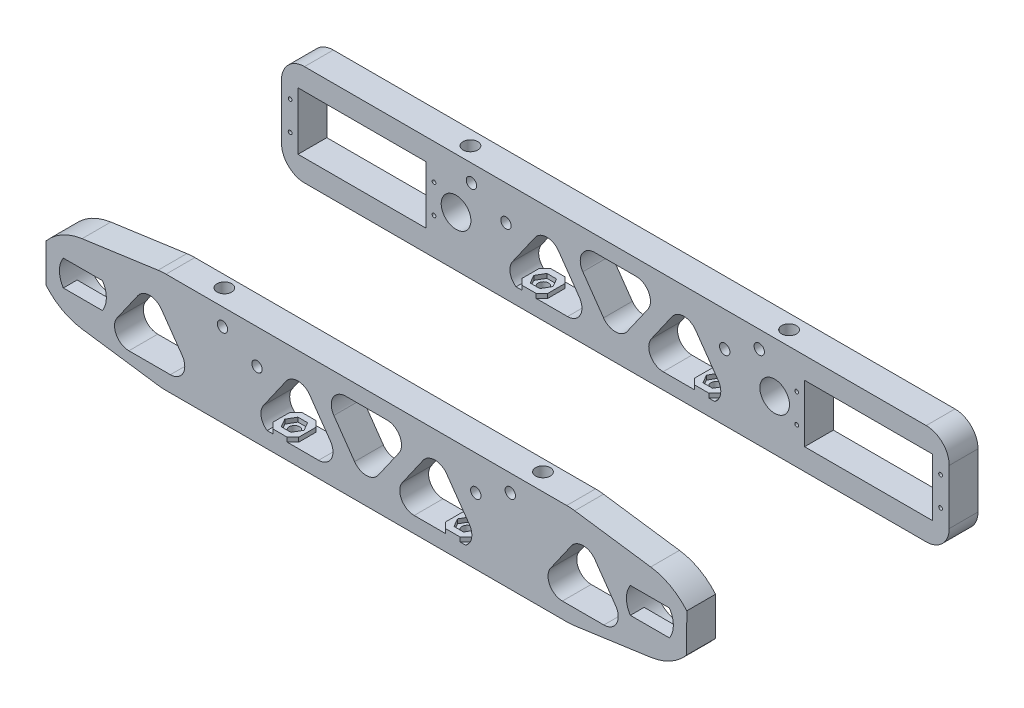
SolidWorks part; units mm, degrees
material "PLA 100% Infill"
ref_plane "Front Plane" through (0, 0, 0) normal (0, 0, 1) x (1, 0, 0)
ref_plane "Top Plane" through (0, 0, 0) normal (0, 1, 0) x (1, 0, 0)
ref_plane "Right Plane" through (0, 0, 0) normal (1, 0, 0) x (0, 0, -1)
sketch "Sketch1" plane through (0, 0, 0) normal (0, 0, 1) x (1, 0, 0)
  line L0 (-232, 17.5) -> (-148.2075, 17.5) construction
  line L1 (-232, 35) -> (0, 35)
  line L2 (-232, 35) -> (-232, 0)
  line L3 (-232, 0) -> (0, 0)
  line L4 (0, 35) -> (0, 0)
  line L5 (-116, 35) -> (-116, 17.5) construction
  line L6 (-156.61, 5.5) -> (-139.805, 29.5)
  line L7 (-139.805, 29.5) -> (-123, 5.5)
  line L8 (-123, 5.5) -> (-156.61, 5.5)
  line L9 (-132.805, 29.5) -> (-116, 5.5)
  line L10 (-116, 5.5) -> (-99.195, 29.5)
  line L11 (-99.195, 29.5) -> (-132.805, 29.5)
  line L12 (-139.805, 29.5) -> (-93.3936, 29.5) construction
  line L13 (-123, 5.5) -> (-123.2541, 5.5) construction
  line L14 (-74.6848, 5.5) -> (-74.6848, 29.5) construction
  line L21 (-116, 17.5) -> (-148.2075, 17.5) construction
  line L22 (-116, 17.5) -> (-83.7925, 17.5) construction
  line L23 (-92.195, 29.5) -> (-109, 5.5)
  line L24 (-75.39, 5.5) -> (-92.195, 29.5)
  line L25 (-109, 5.5) -> (-75.39, 5.5)
  line L27 (-116, 5.5) -> (-116, 0) construction
  circle A2 centre (-171.35, 17.5) radius 5.15
  circle A4 centre (-214.5, 17.5) radius 8.15
  circle A5 centre (-17.5, 17.5) radius 8.15
  circle A6 centre (-60.65, 17.5) radius 5.15
  point P12 (-176.5, 17.5)
  dimension "D2" = 35
  dimension "D3" = 16.3
  dimension "D4" = 10.3
  dimension "D5" = 232
  dimension "D6" = 43.15
  dimension "D7" = 24
  dimension "D9" = 7
  dimension "D10" = 110.7
  dimension "D8" = 70
extrude "Boss-Extrude1" add sketch "Sketch1" along normal blind 10 contours L4 A5 L1 L2 A4 L3 A2 A6 | A4 L2 | L4 A5 | A5 | A4 region at (-116, 32.6537, 0) region at (-214.5, 17.5, 0) region at (-17.5, 17.5, 0)
sketch "Sketch2" plane through (0, 0, 10) normal (0, 0, 1) x (1, 0, 0)
  circle A0 centre (-60.65, 17.5) radius 5.15 construction
  circle A1 centre (-60.65, 17.5) radius 5.15
  circle A2 centre (-171.35, 17.5) radius 5.15 construction
  circle A3 centre (-171.35, 17.5) radius 5.15
extrude "Boss-Extrude2" add sketch "Sketch2" against normal blind 2
ref_plane "Plane1" through (0, 0, -76.5) normal (0, 0, 1) x (1, 0, 0)
sketch "Sketch3" plane through (0, 0, -76.5) normal (0, 0, 1) x (1, 0, 0)
  line L0 (-232, 0) -> (0, 0) construction
  line L1 (-232, 35) -> (0, 35) construction
  line L2 (-232, 0) -> (0, 0)
  line L3 (-232, 35) -> (0, 35)
  line L4 (-181.75, 27.5) -> (-226.25, 27.5)
  line L5 (-181.75, 7.5) -> (-181.75, 27.5)
  line L6 (-226.25, 7.5) -> (-181.75, 7.5)
  line L7 (-226.25, 7.5) -> (-226.25, 27.5)
  line L8 (24, 17.5) -> (-237, 17.5) construction
  line L9 (-229, 22.7282) -> (-229, 12.7282) construction
  line L10 (-179, 22.7282) -> (-179, 12.7282) construction
  line L11 (-179, 12.7282) -> (-184.9311, 12.7282) construction
  line L12 (-116, 35) -> (-116, 0) construction
  line L13 (-50.25, 7.5) -> (-50.25, 27.5)
  line L14 (-5.75, 7.5) -> (-50.25, 7.5)
  line L15 (-5.75, 7.5) -> (-5.75, 27.5)
  line L16 (-50.25, 27.5) -> (-5.75, 27.5)
  line L18 (-92.195, 29.5) -> (-109, 5.5)
  line L21 (0, 35) -> (0, 0) construction
  line L22 (-232, 35) -> (-232, 0) construction
  line L23 (0, 35) -> (0, 0)
  line L24 (-232, 35) -> (-232, 0)
  line L31 (-116, 5.5) -> (-99.195, 29.5) construction
  line L32 (-99.195, 29.5) -> (-132.805, 29.5) construction
  line L33 (-132.805, 29.5) -> (-116, 5.5) construction
  line L34 (-123, 5.5) -> (-156.61, 5.5) construction
  line L35 (-139.805, 29.5) -> (-123, 5.5) construction
  line L36 (-156.61, 5.5) -> (-139.805, 29.5) construction
  line L43 (-116, 5.5) -> (-99.195, 29.5)
  line L44 (-99.195, 29.5) -> (-132.805, 29.5)
  line L45 (-132.805, 29.5) -> (-116, 5.5)
  line L46 (-123, 5.5) -> (-156.61, 5.5)
  line L47 (-139.805, 29.5) -> (-123, 5.5)
  line L48 (-156.61, 5.5) -> (-139.805, 29.5)
  line L49 (-75.39, 5.5) -> (-92.195, 29.5)
  line L50 (-109, 5.5) -> (-75.39, 5.5)
  circle A4 centre (-179, 12.7282) radius 0.65
  circle A5 centre (-179, 22.7282) radius 0.65
  circle A6 centre (-229, 12.7282) radius 0.65
  circle A7 centre (-229, 22.7282) radius 0.65
  circle A8 centre (-171.35, 17.5) radius 5.15 construction
  circle A9 centre (-171.35, 17.5) radius 5.15
  circle A10 centre (-3, 22.7282) radius 0.65
  circle A11 centre (-3, 12.7282) radius 0.65
  circle A12 centre (-53, 12.7282) radius 0.65
  circle A13 centre (-53, 22.7282) radius 0.65
  circle A14 centre (-60.65, 17.5) radius 5.15
  point P5 (-191.5, 17.5)
  point P21 (-181.75, 17.5)
  dimension "D10" = 1.3
  dimension "D1" = 2.75
  dimension "D2" = 20
  dimension "D3" = 44.5
  dimension "D4" = 2.75
  dimension "D5" = 10
  dimension "D6" = 5.2282
  dimension "D7" = 9.75
  dimension "D8" = 10
  dimension "D9" = 131.5
extrude "Boss-Extrude3" add sketch "Sketch3" against normal blind 10 separate body
sketch "Sketch4" plane through (0, 35, 0) normal (0, 1, 0) x (1, 0, 0)
  line L0 (-116, 86.5) -> (-116, -10) construction
  line L1 (0, 86.5) -> (-232, 86.5) construction
  line L2 (-232, -10) -> (0, -10) construction
  line L3 (-171.35, 86.5) -> (-171.35, -10) construction
  line L4 (-243.5, -4) -> (17.5, -4) construction
  line L5 (0, 86.5) -> (0, 76.5) construction
  line L6 (-232, 86.5) -> (-232, 76.5) construction
  line L7 (0, 81.5) -> (-232, 81.5) construction
  line L10 (-177.85, 39) -> (-122.5, 39) construction
  line L11 (-232, -10) -> (0, -10) construction
  circle A4 centre (-171.35, -4) radius 2.55
  circle A11 centre (-60.65, -4) radius 2.55
  circle A12 centre (-171.35, 81.5) radius 2.55
  circle A13 centre (-60.65, 81.5) radius 2.55
  dimension "D1" = 0
  dimension "D4" = 5.1
  dimension "D2" = 55.35
  dimension "D5" = 6
  dimension "D6" = 43
extrude "Cut-Extrude1" cut sketch "Sketch4" against normal blind 10
chamfer "Chamfer1" distance 45 angle 8 4 edges at (0, 35, 5) (0, 0, 5) (-232, 0, 5) (-232, 35, 5) first distance on face at (-171.35, 35, 6.55) first distance on face at (-116, 0, 5)
fillet "Fillet1" radius 8 4 edges at (0, 0, -81.5) (0, 35, -81.5) (-232, 0, -81.5) (-232, 35, -81.5)
sketch "Sketch6" plane through (0, 0, 10) normal (0, 0, 1) x (1, 0, 0)
  line L0 (-116, 5.5) -> (-99.195, 29.5) construction
  line L1 (-174.5, 5.5) -> (-208.11, 5.5)
  line L2 (-132.805, 29.5) -> (-116, 5.5) construction
  line L3 (-208.11, 5.5) -> (-191.305, 29.5)
  line L4 (-139.805, 29.5) -> (-123, 5.5) construction
  line L5 (-156.61, 5.5) -> (-139.805, 29.5) construction
  line L6 (-116, 5.5) -> (-99.195, 29.5)
  line L7 (-99.195, 29.5) -> (-132.805, 29.5)
  line L8 (-132.805, 29.5) -> (-116, 5.5)
  line L9 (-123, 5.5) -> (-156.61, 5.5)
  line L10 (-139.805, 29.5) -> (-123, 5.5)
  line L11 (-156.61, 5.5) -> (-139.805, 29.5)
  line L12 (-191.305, 29.5) -> (-174.5, 5.5)
  line L13 (-109, 5.5) -> (-75.39, 5.5) construction
  line L14 (-75.39, 5.5) -> (-92.195, 29.5) construction
  line L15 (-92.195, 29.5) -> (-109, 5.5) construction
  line L16 (-109, 5.5) -> (-75.39, 5.5)
  line L17 (-75.39, 5.5) -> (-92.195, 29.5)
  line L18 (-92.195, 29.5) -> (-109, 5.5)
  line L19 (-57.5, 5.5) -> (-23.89, 5.5)
  line L20 (-23.89, 5.5) -> (-40.695, 29.5)
  line L21 (-40.695, 29.5) -> (-57.5, 5.5)
  dimension "D3" = 51.5
  dimension "D4" = 51.5
  dimension "D1" = 2
  dimension "D2" = 2
extrude "Cut-Extrude3" cut sketch "Sketch6" against normal blind 10 contours L20 L21 L19 | L1 L3 L12 region at (-40.695, 13.5, 10)
sketch "Sketch7" plane through (0, 5.5, 0) normal (0, 1, 0) x (1, 0, 0)
  line L0 (-156.61, 81.5) -> (-75.39, 81.5) construction
  line L1 (-156.61, 86.5) -> (-156.61, 76.5) construction
  line L2 (-75.39, 86.5) -> (-75.39, 76.5) construction
  line L3 (-227.4452, 0) -> (-227.4452, 76.5) construction
  line L4 (-187, 0) -> (-45, 0) construction
  line L5 (-226.25, 76.5) -> (-181.75, 76.5) construction
  line L6 (-227.4452, 38.25) -> (0, 38.25) construction
  line L7 (0, 38.25) -> (0, 0) construction
  line L8 (-116, 81.5) -> (-116, -5) construction
  line L9 (-116, -10) -> (-116, 0) construction
  line L10 (-149.3486, 81.5) -> (-147.6743, 84.4)
  line L11 (-147.6743, 84.4) -> (-144.3257, 84.4)
  line L12 (-144.3257, 84.4) -> (-142.6514, 81.5)
  line L13 (-142.6514, 81.5) -> (-144.3257, 78.6)
  line L14 (-144.3257, 78.6) -> (-147.6743, 78.6)
  line L15 (-147.6743, 78.6) -> (-149.3486, 81.5)
  line L16 (-144.3257, 84.4) -> (-147.6743, 78.6) construction
  line L17 (-84.3257, 78.6) -> (-82.6514, 81.5)
  line L18 (-87.6743, 78.6) -> (-84.3257, 78.6)
  line L19 (-89.3486, 81.5) -> (-87.6743, 78.6)
  line L20 (-87.6743, 84.4) -> (-89.3486, 81.5)
  line L21 (-84.3257, 84.4) -> (-87.6743, 84.4)
  line L22 (-82.6514, 81.5) -> (-84.3257, 84.4)
  line L23 (-87.6743, -2.1) -> (-84.3257, -2.1)
  line L24 (-89.3486, -5) -> (-87.6743, -2.1)
  line L25 (-87.6743, -7.9) -> (-89.3486, -5)
  line L26 (-84.3257, -7.9) -> (-87.6743, -7.9)
  line L27 (-82.6514, -5) -> (-84.3257, -7.9)
  line L28 (-84.3257, -2.1) -> (-82.6514, -5)
  line L29 (-144.3257, -2.1) -> (-147.6743, -2.1)
  line L30 (-142.6514, -5) -> (-144.3257, -2.1)
  line L31 (-144.3257, -7.9) -> (-142.6514, -5)
  line L32 (-147.6743, -7.9) -> (-144.3257, -7.9)
  line L33 (-149.3486, -5) -> (-147.6743, -7.9)
  line L34 (-147.6743, -2.1) -> (-149.3486, -5)
  line L35 (-156.61, 86.5) -> (-123, 86.5) construction
  line L36 (-150.5, 86.5) -> (-141.5, 86.5)
  line L37 (-150.5, 86.5) -> (-150.5, 76.5)
  line L38 (-150.5, 76.5) -> (-141.5, 76.5)
  line L39 (-141.5, 86.5) -> (-141.5, 76.5)
  line L40 (-156.61, 76.5) -> (-123, 76.5) construction
  line L41 (-150.5, 86.5) -> (-141.5, 76.5) construction
  line L42 (-81.5, 76.5) -> (-90.5, 76.5)
  line L43 (-90.5, 86.5) -> (-90.5, 76.5)
  line L44 (-81.5, 86.5) -> (-90.5, 86.5)
  line L45 (-81.5, 86.5) -> (-81.5, 76.5)
  line L46 (-81.5, -10) -> (-81.5, 0)
  line L47 (-81.5, -10) -> (-90.5, -10)
  line L48 (-90.5, -10) -> (-90.5, 0)
  line L49 (-81.5, 0) -> (-90.5, 0)
  line L50 (-150.5, 0) -> (-141.5, 0)
  line L51 (-141.5, -10) -> (-141.5, 0)
  line L52 (-150.5, -10) -> (-141.5, -10)
  line L53 (-150.5, -10) -> (-150.5, 0)
  circle A2 centre (-146, 81.5) radius 1.8
  circle A3 centre (-86, 81.5) radius 1.8
  circle A4 centre (-86, -5) radius 1.8
  circle A5 centre (-146, -5) radius 1.8
  line M19 (-75.39, 0) -> (-109, 0)
  line M21 (-109, -10) -> (-75.39, -10)
  dimension "D1" = 30
  dimension "D2" = 3.6
  dimension "D3" = 5.8
  dimension "D4" = 9
extrude "Cut-Extrude4" cut sketch "Sketch7" against normal blind 10 contours A5 | A4 | A2 | A3 region at (-146, 5.5, -81.5) region at (-86, 5.5, -81.5) region at (-86, 5.5, 5) region at (-146, 5.5, 5)
extrude "Boss-Extrude4" add sketch "Sketch7<3>" along normal blind 1.5 contours L53 L52 L51 L50 L34 L29 L30 L31 L32 L33 | L48 L46 L23 L28 L27 L26 L25 L24 M21 M19 | L45 L44 L43 L42 L22 L17 L18 L19 L20 L21 | L39 L36 L37 L38 L14 L15 L10 L11 L12 L13 region at (-146, 5.5, -86.3655) region at (-86, 5.5, -76.6345) region at (-86, 5.5, 9.8655) region at (-146, 5.5, 0.1345)
sketch "Sketch7<3>" plane through (0, 5.5, 0) normal (0, 1, 0) x (1, 0, 0) same geometry as "Sketch7"
chamfer "Chamfer2" distance 2 angle 45 8 edges at (-90.5, 6.25, -76.5) (-81.5, 6.25, -76.5) (-81.5, 6.25, -86.5) (-90.5, 6.25, -86.5) (-141.5, 6.25, -86.5) (-150.5, 6.25, -86.5) (-141.5, 6.25, -76.5) (-150.5, 6.25, -76.5)
chamfer "Chamfer3" distance 2 angle 45 8 edges at (-81.5, 6.25, 0) (-81.5, 6.25, 10) (-90.5, 6.25, 10) (-90.5, 6.25, 0) (-141.5, 6.25, 0) (-141.5, 6.25, 10) (-150.5, 6.25, 10) (-150.5, 6.25, 0)
fillet "Fillet2" radius 20 8 edges at (-45, 35, 5) (-45, 0, 5) (0, 6.3243, 5) (0, 28.6757, 5) (-187, 0, 5) (-232, 6.3243, 5) (-232, 28.6757, 5) (-187, 35, 5)
extrude "Cut-Extrude5" cut sketch "Sketch1<3>" along normal blind 5.2 contours A4 | A5 region at (-214.5, 17.5, 0) region at (-17.5, 17.5, 0)
sketch "Sketch1<3>" plane through (0, 0, 0) normal (0, 0, 1) x (1, 0, 0) same geometry as "Sketch1"
sketch "Sketch8" plane through (0, 0, 0) normal (0, 0, -1) x (-1, 0, 0)
  line L0 (10.705, 22) -> (24.295, 22)
  line L1 (10.705, 13) -> (24.295, 13)
  line L2 (207.705, 22) -> (221.295, 22)
  line L3 (207.705, 13) -> (221.295, 13)
  circle A3 centre (214.5, 17.5) radius 8.15 construction
  arc A4 (207.705, 22) -> (207.705, 13) centre (214.5, 17.5) ccw
  circle A5 centre (17.5, 17.5) radius 8.15 construction
  arc A6 (10.705, 22) -> (10.705, 13) centre (17.5, 17.5) ccw
  arc A7 (24.295, 13) -> (24.295, 22) centre (17.5, 17.5) ccw
  arc A8 (221.295, 13) -> (221.295, 22) centre (214.5, 17.5) ccw
  dimension "D1" = 4.5
  dimension "D2" = 4.5
extrude "Cut-Extrude6" cut sketch "Sketch8" against normal through all
sketch "Sketch9" plane through (0, 25, 0) normal (0, 1, 0) x (1, 0, 0)
  line L0 (-60.65, 81.5) -> (-60.65, -4) construction
  line L1 (-60.65, -4) -> (-171.35, -4) construction
  line L2 (-116, -4) -> (-116, 76.5) construction
  line L3 (-60.65, 38.75) -> (-116, 38.75) construction
  circle A0 centre (-171.35, -4) radius 0.65
  circle A2 centre (-60.65, -4) radius 0.65
  circle A3 centre (-60.65, 81.5) radius 0.65
  circle A4 centre (-171.35, 81.5) radius 0.65
  dimension "D1" = 1.3
extrude "Cut-Extrude7" cut sketch "Sketch9" against normal blind 5.2
fillet "Fillet3" radius 5 9 edges at (-92.195, 29.5, -81.5) (-109, 5.5, -81.5) (-139.805, 29.5, -81.5) (-123, 5.5, -81.5) (-116, 5.5, -81.5) (-99.195, 29.5, -81.5) (-132.805, 29.5, -81.5) (-75.39, 5.5, -81.5) (-156.61, 5.5, -81.5)
fillet "Fillet4" radius 5 15 edges at (-191.305, 29.5, 5) (-139.805, 29.5, 5) (-92.195, 29.5, 5) (-40.695, 29.5, 5) (-174.5, 5.5, 5) (-123, 5.5, 5) (-23.89, 5.5, 5) (-208.11, 5.5, 5) (-109, 5.5, 5) (-57.5, 5.5, 5) (-75.39, 5.5, 5) (-156.61, 5.5, 5) (-132.805, 29.5, 5) (-99.195, 29.5, 5) (-116, 5.5, 5)
chamfer "Chamfer4" [suppressed] distance 8 angle 55
chamfer "Chamfer5" [suppressed] distance 8 angle 55
sketch "Sketch12" [suppressed] plane through (0, 22.9468, 0) normal (0, -1, 0) x (1, 0, 0)
  line L6 (-150.8936, 0) -> (-150.8936, 10)
  line L9 (-150.8936, 0) -> (-141.7164, 0)
  line L11 (-150.8936, 10) -> (-141.7164, 10)
  line L12 (-141.7164, 10) -> (-141.7164, 0)
  line L13 (-94.1064, 10) -> (-103.2836, 0) construction
  line L14 (-97.0071, 7.8765) -> (-100.3558, 7.8765)
  line L15 (-100.3558, 7.8765) -> (-102.0301, 4.9765)
  line L24 (-94.1064, 10) -> (-103.2836, 10)
  line L25 (-103.2836, 10) -> (-103.2836, 0)
  line L26 (-103.2836, 0) -> (-94.1064, 0)
  line L27 (-94.1064, 0) -> (-94.1064, 10)
  line L28 (-94.1064, 10) -> (-103.2836, 10)
  line L29 (-103.2836, 10) -> (-103.2836, 0)
  line L30 (-103.2836, 0) -> (-94.1064, 0)
  line L31 (-94.1064, 0) -> (-94.1064, 10)
  line L32 (-150.8936, -86.5) -> (-141.7164, -86.5)
  line L33 (-141.7164, -86.5) -> (-141.7164, -76.5)
  line L34 (-141.7164, -76.5) -> (-150.8936, -76.5)
  line L35 (-150.8936, -76.5) -> (-150.8936, -86.5)
  line L36 (-150.8936, -86.5) -> (-141.7164, -86.5)
  line L37 (-141.7164, -86.5) -> (-141.7164, -76.5)
  line L38 (-141.7164, -76.5) -> (-150.8936, -76.5)
  line L39 (-150.8936, -76.5) -> (-150.8936, -86.5)
  line L40 (-103.2836, -86.5) -> (-94.1064, -86.5)
  line L41 (-94.1064, -86.5) -> (-94.1064, -76.5)
  line L42 (-94.1064, -76.5) -> (-103.2836, -76.5)
  line L43 (-103.2836, -76.5) -> (-103.2836, -86.5)
  line L44 (-103.2836, -86.5) -> (-94.1064, -86.5)
  line L45 (-94.1064, -86.5) -> (-94.1064, -76.5)
  line L46 (-94.1064, -76.5) -> (-103.2836, -76.5)
  line L47 (-103.2836, -76.5) -> (-103.2836, -86.5)
  line L48 (-102.0301, 4.9765) -> (-100.3558, 2.0765)
  line L49 (-100.3558, 2.0765) -> (-97.0071, 2.0765)
  line L50 (-97.0071, 2.0765) -> (-95.3328, 4.9765)
  line L51 (-95.3328, 4.9765) -> (-97.0071, 7.8765)
  line L52 (-100.3558, 7.8765) -> (-97.0071, 2.0765) construction
  line L59 (-94.1064, -76.5) -> (-103.2836, -86.5) construction
  line L60 (-141.7164, -76.5) -> (-150.8936, -86.5) construction
  line L61 (-97.0207, -78.6) -> (-100.3693, -78.6)
  line L62 (-100.3693, -78.6) -> (-102.0437, -81.5)
  line L63 (-102.0437, -81.5) -> (-100.3693, -84.4)
  line L64 (-100.3693, -84.4) -> (-97.0207, -84.4)
  line L65 (-97.0207, -84.4) -> (-95.3464, -81.5)
  line L66 (-95.3464, -81.5) -> (-97.0207, -78.6)
  line L67 (-100.3693, -78.6) -> (-97.0207, -84.4) construction
  line L68 (-144.6307, -78.6) -> (-147.9793, -78.6)
  line L69 (-147.9793, -78.6) -> (-149.6536, -81.5)
  line L70 (-149.6536, -81.5) -> (-147.9793, -84.4)
  line L71 (-147.9793, -84.4) -> (-144.6307, -84.4)
  line L72 (-144.6307, -84.4) -> (-142.9563, -81.5)
  line L73 (-142.9563, -81.5) -> (-144.6307, -78.6)
  line L74 (-147.9793, -78.6) -> (-144.6307, -84.4) construction
  line L75 (-144.6307, 7.9) -> (-147.9793, 7.9)
  line L76 (-147.9793, 7.9) -> (-149.6536, 5)
  line L77 (-149.6536, 5) -> (-147.9793, 2.1)
  line L78 (-147.9793, 2.1) -> (-144.6307, 2.1)
  line L79 (-144.6307, 2.1) -> (-142.9563, 5)
  line L80 (-142.9563, 5) -> (-144.6307, 7.9)
  line L81 (-147.9793, 7.9) -> (-144.6307, 2.1) construction
  line L82 (-141.7164, 10) -> (-150.8936, 0) construction
  line L83 (-230.8579, 0) -> (-14.1421, 0) construction
  circle A1 centre (-98.695, 5) radius 1.8
  circle A3 centre (-98.695, -81.5) radius 1.8
  circle A4 centre (-146.305, -81.5) radius 1.8
  circle A5 centre (-146.305, 5) radius 1.8
  point P36 (-146.305, 5)
  point P57 (-146.305, 5)
  point P61 (-98.695, -81.5)
  point P64 (-146.305, -81.5)
  dimension "D1" = 3.6
  dimension "D5" = 3.6
  dimension "D12" = 3.6
  dimension "D16" = 3.6
  dimension "D2" = 5.8
  dimension "D3" = 5.8
  dimension "D4" = 5.8
  dimension "D10" = 5.8
  dimension "D11" = 5.8
  dimension "D6" = 5.8
  dimension "D13" = 5.8
  dimension "D14" = 5.8
  dimension "D15" = 5.8
  dimension "D17" = 5.8
  dimension "D18" = 5.8
  dimension "D19" = 5.8
  dimension "D7" = 0
  dimension "D8" = 0
  dimension "D9" = 0
extrude "Cut-Extrude8" [suppressed] cut sketch "Sketch12" against normal blind 1.5 contours L79 L80 L75 L76 L77 L78 A5 | A5 | L50 L51 L14 L15 L48 L49 A1 | A1 | L65 L66 L61 L62 L63 L64 A3 | A3 | L72 L73 L68 L69 L70 L71 A4 | A4
sketch "Sketch13" [suppressed] plane through (0, 22.9468, 0) normal (0, -1, 0) x (1, 0, 0)
  line L4 (-150.8936, -86.5) -> (-141.7164, -86.5)
  line L5 (-141.7164, -86.5) -> (-141.7164, -76.5)
  line L6 (-97.0071, 7.8765) -> (-100.3558, 7.8765)
  line L7 (-100.3558, 7.8765) -> (-102.0301, 4.9765)
  line L8 (-102.0301, 4.9765) -> (-100.3558, 2.0765)
  line L9 (-100.3558, 2.0765) -> (-97.0071, 2.0765)
  line L10 (-97.0071, 2.0765) -> (-95.3328, 4.9765)
  line L11 (-95.3328, 4.9765) -> (-97.0071, 7.8765)
  line L12 (-97.0071, 7.8765) -> (-100.3558, 7.8765)
  line L13 (-100.3558, 7.8765) -> (-102.0301, 4.9765)
  line L14 (-102.0301, 4.9765) -> (-100.3558, 2.0765)
  line L15 (-100.3558, 2.0765) -> (-97.0071, 2.0765)
  line L16 (-97.0071, 2.0765) -> (-95.3328, 4.9765)
  line L17 (-95.3328, 4.9765) -> (-97.0071, 7.8765)
  line L18 (-97.0207, -84.4) -> (-95.3464, -81.5)
  line L19 (-95.3464, -81.5) -> (-97.0207, -78.6)
  line L20 (-97.0207, -78.6) -> (-100.3693, -78.6)
  line L21 (-100.3693, -78.6) -> (-102.0437, -81.5)
  line L22 (-102.0437, -81.5) -> (-100.3693, -84.4)
  line L23 (-100.3693, -84.4) -> (-97.0207, -84.4)
  line L24 (-97.0207, -84.4) -> (-95.3464, -81.5)
  line L25 (-95.3464, -81.5) -> (-97.0207, -78.6)
  line L26 (-97.0207, -78.6) -> (-100.3693, -78.6)
  line L27 (-100.3693, -78.6) -> (-102.0437, -81.5)
  line L28 (-102.0437, -81.5) -> (-100.3693, -84.4)
  line L29 (-100.3693, -84.4) -> (-97.0207, -84.4)
  line L30 (-141.7164, -76.5) -> (-150.8936, -76.5)
  line L31 (-150.8936, -76.5) -> (-150.8936, -86.5)
  line L32 (-150.8936, -86.5) -> (-141.7164, -86.5)
  line L33 (-141.7164, -86.5) -> (-141.7164, -76.5)
  line L34 (-141.7164, -76.5) -> (-150.8936, -76.5)
  line L35 (-150.8936, -76.5) -> (-150.8936, -86.5)
  line L36 (-94.1064, 10) -> (-103.2836, 10)
  line L37 (-103.2836, 10) -> (-103.2836, 0)
  line L38 (-103.2836, 0) -> (-94.1064, 0)
  line L39 (-94.1064, 0) -> (-94.1064, 10)
  line L40 (-94.1064, 10) -> (-103.2836, 10)
  line L41 (-103.2836, 10) -> (-103.2836, 0)
  line L42 (-103.2836, 0) -> (-94.1064, 0)
  line L43 (-94.1064, 0) -> (-94.1064, 10)
  line L44 (-150.8936, 0) -> (-141.7164, 0)
  line L45 (-141.7164, 0) -> (-141.7164, 10)
  line L46 (-141.7164, 10) -> (-150.8936, 10)
  line L47 (-150.8936, 10) -> (-150.8936, 0)
  line L48 (-150.8936, 0) -> (-141.7164, 0)
  line L49 (-141.7164, 0) -> (-141.7164, 10)
  line L50 (-141.7164, 10) -> (-150.8936, 10)
  line L51 (-150.8936, 10) -> (-150.8936, 0)
  line L52 (-94.1064, -76.5) -> (-103.2836, -76.5)
  line L53 (-94.1064, -86.5) -> (-94.1064, -76.5)
  line L54 (-144.6307, -78.6) -> (-147.9793, -78.6)
  line L55 (-147.9793, -78.6) -> (-149.6536, -81.5)
  line L56 (-149.6536, -81.5) -> (-147.9793, -84.4)
  line L57 (-147.9793, -84.4) -> (-144.6307, -84.4)
  line L58 (-144.6307, -84.4) -> (-142.9563, -81.5)
  line L59 (-142.9563, -81.5) -> (-144.6307, -78.6)
  line L60 (-144.6307, -78.6) -> (-147.9793, -78.6)
  line L61 (-147.9793, -78.6) -> (-149.6536, -81.5)
  line L62 (-149.6536, -81.5) -> (-147.9793, -84.4)
  line L63 (-147.9793, -84.4) -> (-144.6307, -84.4)
  line L64 (-144.6307, -84.4) -> (-142.9563, -81.5)
  line L65 (-142.9563, -81.5) -> (-144.6307, -78.6)
  line L66 (-103.2836, -86.5) -> (-94.1064, -86.5)
  line L67 (-103.2836, -76.5) -> (-103.2836, -86.5)
  line L68 (-94.1064, -76.5) -> (-103.2836, -76.5)
  line L69 (-94.1064, -86.5) -> (-94.1064, -76.5)
  line L70 (-103.2836, -86.5) -> (-94.1064, -86.5)
  line L71 (-103.2836, -76.5) -> (-103.2836, -86.5)
  line L74 (-144.6307, 7.9) -> (-147.9793, 7.9)
  line L75 (-147.9793, 7.9) -> (-149.6536, 5)
  line L76 (-149.6536, 5) -> (-147.9793, 2.1)
  line L77 (-147.9793, 2.1) -> (-144.6307, 2.1)
  line L78 (-144.6307, 2.1) -> (-142.9563, 5)
  line L79 (-142.9563, 5) -> (-144.6307, 7.9)
  line L80 (-144.6307, 7.9) -> (-147.9793, 7.9)
  line L81 (-147.9793, 7.9) -> (-149.6536, 5)
  line L82 (-149.6536, 5) -> (-147.9793, 2.1)
  line L83 (-147.9793, 2.1) -> (-144.6307, 2.1)
  line L84 (-144.6307, 2.1) -> (-142.9563, 5)
  line L85 (-142.9563, 5) -> (-144.6307, 7.9)
  circle A1 centre (-98.695, -81.5) radius 1.8
  circle A2 centre (-98.695, -81.5) radius 1.8
  circle A3 centre (-98.695, 5) radius 1.8
  circle A4 centre (-98.695, 5) radius 1.8
  circle A5 centre (-146.305, -81.5) radius 1.8
  circle A6 centre (-146.305, -81.5) radius 1.8
  circle A7 centre (-146.305, 5) radius 1.8
  circle A8 centre (-146.305, 5) radius 1.8
  dimension "D1" = 0
  dimension "D2" = 0
  dimension "D3" = 0
  dimension "D4" = 0
  dimension "D5" = 0
  dimension "D6" = 0
  dimension "D7" = 0
  dimension "D8" = 0
  dimension "D9" = 0
  dimension "D10" = 0
  dimension "D11" = 0
  dimension "D12" = 0
extrude "Cut-Extrude9" [suppressed] cut sketch "Sketch13" against normal through all contours A4 | A8 | A6 | A2
fillet "Fillet5" [suppressed] radius 5
chamfer "Chamfer6" distance 12 angle 18 2 edges at (-231.0114, 17.5, 5) (-0.9886, 17.5, 5) first distance on face at (-223.8706, 9.5407, 5) first distance on face at (-8.1294, 9.5407, 5)
sketch "Sketch14" plane through (0, 0, -86.5) normal (0, 0, -1) x (-1, 0, 0)
  line L0 (116, 35) -> (116, 0) construction
  line L1 (8, 35) -> (224, 35) construction
  line L2 (224, 0) -> (8, 0) construction
  circle A0 centre (78, 23) radius 1.8
  circle A1 centre (66, 29) radius 1.8
  circle A2 centre (166, 29) radius 1.8
  circle A3 centre (154, 23) radius 1.8
  dimension "D1" = 3.6
  dimension "D2" = 3.6
  dimension "D3" = 6
  dimension "D4" = 38
  dimension "D5" = 12
  dimension "D6" = 23
extrude "Cut-Extrude10" cut sketch "Sketch14" against normal through all
